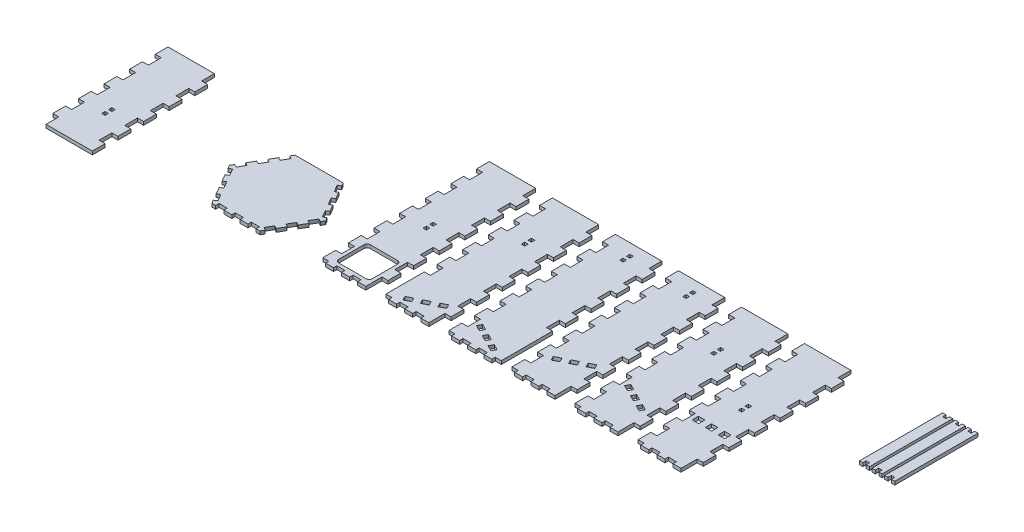
SolidWorks part; units mm, degrees
ref_plane "Front Plane" through (0, 0, 0) normal (0, 0, 1) x (1, 0, 0)
ref_plane "Top Plane" through (0, 0, 0) normal (0, 1, 0) x (1, 0, 0)
ref_plane "Right Plane" through (0, 0, 0) normal (1, 0, 0) x (0, 0, -1)
sketch "Sketch1" plane through (0, 0, 0) normal (0, 1, 0) x (1, 0, 0)
  line L0 (-22.87, -39.612) -> (-19.175, -39.612)
  line L13 (-19.175, -39.612) -> (-19.175, -36.412)
  line L14 (-19.175, -36.412) -> (-11.505, -36.412)
  line L15 (-11.505, -36.412) -> (-11.505, -39.612)
  line L16 (-11.505, -39.612) -> (-3.835, -39.612)
  line L17 (-3.835, -39.612) -> (-3.835, -36.412)
  line L18 (-3.835, -36.412) -> (3.835, -36.412)
  line L19 (3.835, -36.412) -> (3.835, -39.612)
  line L21 (-45.74, 0) -> (-43.8925, -3.2)
  line L22 (3.835, -39.612) -> (11.505, -39.612)
  line L23 (11.505, -39.612) -> (11.505, -36.412)
  line L24 (11.505, -36.412) -> (19.175, -36.412)
  line L25 (19.175, -36.412) -> (19.175, -39.612)
  line L26 (19.175, -39.612) -> (22.87, -39.612)
  line L27 (22.87, -39.612) -> (24.7175, -36.412)
  line L28 (45.74, 0) -> (22.87, 39.612) construction
  line L29 (24.7175, -36.412) -> (21.9462, -34.812)
  line L30 (21.9462, -34.812) -> (25.7812, -28.1696)
  line L31 (25.7812, -28.1696) -> (28.5525, -29.7696)
  line L32 (28.5525, -29.7696) -> (32.3875, -23.1272)
  line L33 (32.3875, -23.1272) -> (29.6162, -21.5272)
  line L34 (29.6162, -21.5272) -> (33.4512, -14.8848)
  line L35 (33.4512, -14.8848) -> (36.2225, -16.4848)
  line L36 (36.2225, -16.4848) -> (40.0575, -9.8424)
  line L37 (40.0575, -9.8424) -> (37.2862, -8.2424)
  line L38 (37.2862, -8.2424) -> (41.1212, -1.6)
  line L39 (41.1212, -1.6) -> (43.8925, -3.2)
  line L40 (43.8925, -3.2) -> (45.74, 0)
  line L41 (45.74, 0) -> (43.8925, 3.2)
  line L42 (22.87, 39.612) -> (-22.87, 39.612) construction
  line L43 (-22.87, 39.612) -> (-45.74, 0) construction
  line L44 (43.8925, 3.2) -> (41.1212, 1.6)
  line L45 (41.1212, 1.6) -> (37.2862, 8.2424)
  line L46 (37.2862, 8.2424) -> (40.0575, 9.8424)
  line L47 (40.0575, 9.8424) -> (36.2225, 16.4848)
  line L48 (36.2225, 16.4848) -> (33.4512, 14.8848)
  line L49 (33.4512, 14.8848) -> (29.6162, 21.5272)
  line L50 (29.6162, 21.5272) -> (32.3875, 23.1272)
  line L51 (32.3875, 23.1272) -> (28.5525, 29.7696)
  line L52 (28.5525, 29.7696) -> (25.7812, 28.1696)
  line L53 (25.7812, 28.1696) -> (21.9462, 34.812)
  line L54 (21.9462, 34.812) -> (24.7175, 36.412)
  line L55 (24.7175, 36.412) -> (22.87, 39.612)
  line L57 (-45.74, 0) -> (-22.87, -39.612) construction
  line L58 (-22.87, -39.612) -> (22.87, -39.612) construction
  line L71 (-22.87, 39.612) -> (-24.7175, 36.412)
  line L72 (22.87, -39.612) -> (45.74, 0) construction
  line L73 (-43.8925, -3.2) -> (-41.1212, -1.6)
  line L74 (-24.7175, 36.412) -> (-21.9462, 34.812)
  line L75 (-21.9462, 34.812) -> (-25.7812, 28.1696)
  line L76 (-25.7812, 28.1696) -> (-28.5525, 29.7696)
  line L77 (-28.5525, 29.7696) -> (-32.3875, 23.1272)
  line L78 (-32.3875, 23.1272) -> (-29.6162, 21.5272)
  line L79 (-29.6162, 21.5272) -> (-33.4512, 14.8848)
  line L80 (-33.4512, 14.8848) -> (-36.2225, 16.4848)
  line L81 (-36.2225, 16.4848) -> (-40.0575, 9.8424)
  line L82 (-40.0575, 9.8424) -> (-37.2862, 8.2424)
  line L83 (-37.2862, 8.2424) -> (-41.1212, 1.6)
  line L84 (-41.1212, 1.6) -> (-43.8925, 3.2)
  line L85 (-43.8925, 3.2) -> (-45.74, 0)
  line L86 (-41.1212, -1.6) -> (-37.2862, -8.2424)
  line L87 (-37.2862, -8.2424) -> (-40.0575, -9.8424)
  line L88 (-40.0575, -9.8424) -> (-36.2225, -16.4848)
  line L89 (-36.2225, -16.4848) -> (-33.4512, -14.8848)
  line L90 (-33.4512, -14.8848) -> (-29.6162, -21.5272)
  line L91 (-29.6162, -21.5272) -> (-32.3875, -23.1272)
  line L92 (-32.3875, -23.1272) -> (-28.5525, -29.7696)
  line L93 (-28.5525, -29.7696) -> (-25.7812, -28.1696)
  line L94 (-25.7812, -28.1696) -> (-21.9462, -34.812)
  line L95 (-21.9462, -34.812) -> (-24.7175, -36.412)
  line L96 (-24.7175, -36.412) -> (-22.87, -39.612)
  line L97 (-21.9462, -34.812) -> (-19.175, -39.612) construction
  line L102 (19.175, -36.412) -> (24.7175, -36.412) construction
  line L103 (-19.175, -36.412) -> (-24.7175, -36.412) construction
  line L104 (80.5528, -34.8794) -> (88.2227, -34.8794)
  line L105 (88.2227, -34.8794) -> (88.2227, -31.6794)
  line L106 (88.2227, -31.6794) -> (95.8927, -31.6794)
  line L107 (95.8927, -31.6794) -> (95.8927, -34.8794)
  line L108 (95.8927, -34.8794) -> (103.5627, -34.8794)
  line L109 (103.5627, -34.8794) -> (103.5627, -31.6794)
  line L110 (103.5627, -31.6794) -> (111.2327, -31.6794)
  line L111 (111.2327, -31.6794) -> (111.2327, -34.8794)
  line L112 (111.2327, -34.8794) -> (118.9027, -34.8794)
  line L113 (80.5528, -34.8794) -> (80.5528, -31.6794)
  line L114 (80.5528, -31.6794) -> (74.8102, -31.6794)
  line L115 (74.8102, -31.6794) -> (74.8102, -19.4911)
  line L116 (74.8102, -19.4911) -> (80.5528, -19.4911)
  line L117 (80.5528, -19.4911) -> (80.5528, -7.3028)
  line L118 (80.5528, -7.3028) -> (74.8102, -7.3028)
  line L121 (118.9027, -7.3028) -> (124.6452, -7.3028)
  line L122 (124.6452, -7.3028) -> (124.6452, -19.4911)
  line L123 (124.6452, -19.4911) -> (118.9027, -19.4911)
  line L124 (118.9027, -19.4911) -> (118.9027, -34.8794)
  line L126 (21.9462, -34.812) -> (19.175, -39.612) construction
  line L250 (140.5528, -34.8794) -> (148.2227, -34.8794)
  line L265 (148.2227, -34.8794) -> (148.2227, -31.6794)
  line L266 (148.2227, -31.6794) -> (155.8927, -31.6794)
  line L267 (155.8927, -31.6794) -> (155.8927, -34.8794)
  line L268 (155.8927, -34.8794) -> (163.5627, -34.8794)
  line L269 (163.5627, -34.8794) -> (163.5627, -31.6794)
  line L270 (74.8102, -7.3028) -> (74.8102, 4.8855)
  line L271 (74.8102, 4.8855) -> (80.5528, 4.8855)
  line L272 (80.5528, 4.8855) -> (80.5528, 17.0739)
  line L273 (80.5528, 17.0739) -> (74.8102, 17.0739)
  line L274 (74.8102, 17.0739) -> (74.8102, 29.2622)
  line L275 (74.8102, 29.2622) -> (80.5528, 29.2622)
  line L276 (80.5528, 29.2622) -> (80.5528, 41.4505)
  line L277 (80.5528, 41.4505) -> (74.8102, 41.4505)
  line L278 (74.8102, 41.4505) -> (74.8102, 53.6388)
  line L279 (74.8102, 53.6388) -> (80.5528, 53.6388)
  line L280 (80.5528, 53.6388) -> (80.5528, 65.8271)
  line L281 (80.5528, 65.8271) -> (74.8102, 65.8271)
  line L282 (74.8102, 65.8271) -> (74.8102, 78.0154)
  line L283 (74.8102, 78.0154) -> (80.5528, 78.0154)
  line L284 (80.5528, 78.0154) -> (80.5528, 90.2037)
  line L285 (80.5528, 90.2037) -> (74.8102, 90.2037)
  line L286 (74.8102, 90.2037) -> (74.8102, 102.392)
  line L287 (74.8102, 102.392) -> (80.5528, 102.392)
  line L288 (80.5528, 102.392) -> (80.5528, 114.5803)
  line L289 (80.5528, 114.5803) -> (74.8102, 114.5803)
  line L290 (74.8102, 114.5803) -> (74.8102, 126.7686)
  line L291 (118.9027, -7.3028) -> (118.9027, 4.8855)
  line L292 (118.9027, 4.8855) -> (124.6452, 4.8855)
  line L293 (124.6452, 4.8855) -> (124.6452, 17.0739)
  line L294 (124.6452, 17.0739) -> (118.9027, 17.0739)
  line L295 (118.9027, 17.0739) -> (118.9027, 29.2622)
  line L296 (118.9027, 29.2622) -> (124.6452, 29.2622)
  line L297 (124.6452, 29.2622) -> (124.6452, 41.4505)
  line L298 (124.6452, 41.4505) -> (118.9027, 41.4505)
  line L299 (118.9027, 41.4505) -> (118.9027, 53.6388)
  line L300 (118.9027, 53.6388) -> (124.6452, 53.6388)
  line L301 (124.6452, 53.6388) -> (124.6452, 65.8271)
  line L302 (124.6452, 65.8271) -> (118.9027, 65.8271)
  line L303 (118.9027, 65.8271) -> (118.9027, 78.0154)
  line L304 (118.9027, 78.0154) -> (124.6452, 78.0154)
  line L305 (124.6452, 78.0154) -> (124.6452, 90.2037)
  line L306 (124.6452, 90.2037) -> (118.9027, 90.2037)
  line L307 (118.9027, 90.2037) -> (118.9027, 102.392)
  line L308 (118.9027, 102.392) -> (124.6452, 102.392)
  line L309 (124.6452, 102.392) -> (124.6452, 114.5803)
  line L310 (124.6452, 114.5803) -> (118.9027, 114.5803)
  line L311 (118.9027, 114.5803) -> (118.9027, 126.7686)
  line L312 (163.5627, -31.6794) -> (171.2327, -31.6794)
  line L313 (171.2327, -31.6794) -> (171.2327, -34.8794)
  line L314 (171.2327, -34.8794) -> (178.9027, -34.8794)
  line L315 (140.5528, -34.8794) -> (140.5528, -31.6794)
  line L316 (140.5528, -31.6794) -> (134.8102, -31.6794)
  line L317 (134.8102, -31.6794) -> (134.8102, -19.4911)
  line L322 (178.9027, -7.3028) -> (184.6452, -7.3028)
  line L323 (184.6452, -7.3028) -> (184.6452, -19.4911)
  line L324 (184.6452, -19.4911) -> (178.9027, -19.4911)
  line L325 (178.9027, -19.4911) -> (178.9027, -34.8794)
  line L326 (134.8102, -7.3028) -> (134.8102, 4.8855)
  line L327 (134.8102, 4.8855) -> (140.5528, 4.8855)
  line L328 (140.5528, 4.8855) -> (140.5528, 17.0739)
  line L329 (140.5528, 17.0739) -> (134.8102, 17.0739)
  line L330 (134.8102, 17.0739) -> (134.8102, 29.2622)
  line L331 (134.8102, 29.2622) -> (140.5528, 29.2622)
  line L332 (140.5528, 29.2622) -> (140.5528, 41.4505)
  line L333 (140.5528, 41.4505) -> (134.8102, 41.4505)
  line L334 (134.8102, 41.4505) -> (134.8102, 53.6388)
  line L335 (134.8102, 53.6388) -> (140.5528, 53.6388)
  line L336 (140.5528, 53.6388) -> (140.5528, 65.8271)
  line L337 (140.5528, 65.8271) -> (134.8102, 65.8271)
  line L338 (134.8102, 65.8271) -> (134.8102, 78.0154)
  line L339 (134.8102, 78.0154) -> (140.5528, 78.0154)
  line L340 (140.5528, 78.0154) -> (140.5528, 90.2037)
  line L341 (140.5528, 90.2037) -> (134.8102, 90.2037)
  line L342 (134.8102, 90.2037) -> (134.8102, 102.392)
  line L343 (134.8102, 102.392) -> (140.5528, 102.392)
  line L344 (140.5528, 102.392) -> (140.5528, 114.5803)
  line L345 (140.5528, 114.5803) -> (134.8102, 114.5803)
  line L346 (134.8102, 114.5803) -> (134.8102, 126.7686)
  line L347 (178.9027, -7.3028) -> (178.9027, 4.8855)
  line L348 (178.9027, 4.8855) -> (184.6452, 4.8855)
  line L349 (184.6452, 4.8855) -> (184.6452, 17.0739)
  line L350 (184.6452, 17.0739) -> (178.9027, 17.0739)
  line L351 (178.9027, 17.0739) -> (178.9027, 29.2622)
  line L352 (178.9027, 29.2622) -> (184.6452, 29.2622)
  line L353 (184.6452, 29.2622) -> (184.6452, 41.4505)
  line L354 (184.6452, 41.4505) -> (178.9027, 41.4505)
  line L355 (178.9027, 41.4505) -> (178.9027, 53.6388)
  line L356 (178.9027, 53.6388) -> (184.6452, 53.6388)
  line L357 (184.6452, 53.6388) -> (184.6452, 65.8271)
  line L358 (184.6452, 65.8271) -> (178.9027, 65.8271)
  line L359 (178.9027, 65.8271) -> (178.9027, 78.0154)
  line L360 (178.9027, 78.0154) -> (184.6452, 78.0154)
  line L361 (184.6452, 78.0154) -> (184.6452, 90.2037)
  line L362 (184.6452, 90.2037) -> (178.9027, 90.2037)
  line L363 (178.9027, 90.2037) -> (178.9027, 102.392)
  line L364 (178.9027, 102.392) -> (184.6452, 102.392)
  line L365 (184.6452, 102.392) -> (184.6452, 114.5803)
  line L366 (184.6452, 114.5803) -> (178.9027, 114.5803)
  line L367 (178.9027, 114.5803) -> (178.9027, 126.7686)
  line L369 (200.5528, -34.8794) -> (208.2227, -34.8794)
  line L370 (208.2227, -34.8794) -> (208.2227, -31.6794)
  line L371 (208.2227, -31.6794) -> (215.8927, -31.6794)
  line L372 (215.8927, -31.6794) -> (215.8927, -34.8794)
  line L373 (215.8927, -34.8794) -> (223.5627, -34.8794)
  line L374 (223.5627, -34.8794) -> (223.5627, -31.6794)
  line L375 (223.5627, -31.6794) -> (231.2327, -31.6794)
  line L376 (231.2327, -31.6794) -> (231.2327, -34.8794)
  line L377 (231.2327, -34.8794) -> (238.9027, -34.8794)
  line L378 (200.5528, -34.8794) -> (200.5528, -31.6794)
  line L379 (200.5528, -31.6794) -> (194.8102, -31.6794)
  line L380 (194.8102, -31.6794) -> (194.8102, -19.4911)
  line L381 (194.8102, -19.4911) -> (200.5528, -19.4911)
  line L382 (200.5528, -19.4911) -> (200.5528, -7.3028)
  line L383 (200.5528, -7.3028) -> (194.8102, -7.3028)
  line L386 (244.6452, -7.3028) -> (244.6452, -19.4911)
  line L389 (194.8102, -7.3028) -> (194.8102, 4.8855)
  line L390 (194.8102, 4.8855) -> (200.5528, 4.8855)
  line L391 (200.5528, 4.8855) -> (200.5528, 17.0739)
  line L392 (200.5528, 17.0739) -> (194.8102, 17.0739)
  line L393 (194.8102, 17.0739) -> (194.8102, 29.2622)
  line L394 (194.8102, 29.2622) -> (200.5528, 29.2622)
  line L395 (200.5528, 29.2622) -> (200.5528, 41.4505)
  line L396 (200.5528, 41.4505) -> (194.8102, 41.4505)
  line L397 (194.8102, 41.4505) -> (194.8102, 53.6388)
  line L398 (194.8102, 53.6388) -> (200.5528, 53.6388)
  line L399 (200.5528, 53.6388) -> (200.5528, 65.8271)
  line L400 (200.5528, 65.8271) -> (194.8102, 65.8271)
  line L401 (194.8102, 65.8271) -> (194.8102, 78.0154)
  line L402 (194.8102, 78.0154) -> (200.5528, 78.0154)
  line L403 (200.5528, 78.0154) -> (200.5528, 90.2037)
  line L404 (200.5528, 90.2037) -> (194.8102, 90.2037)
  line L405 (194.8102, 90.2037) -> (194.8102, 102.392)
  line L406 (194.8102, 102.392) -> (200.5528, 102.392)
  line L407 (200.5528, 102.392) -> (200.5528, 114.5803)
  line L408 (200.5528, 114.5803) -> (194.8102, 114.5803)
  line L409 (194.8102, 114.5803) -> (194.8102, 126.7686)
  line L413 (244.6452, 17.0739) -> (238.9027, 17.0739)
  line L414 (238.9027, 17.0739) -> (238.9027, 29.2622)
  line L415 (238.9027, 29.2622) -> (244.6452, 29.2622)
  line L416 (244.6452, 29.2622) -> (244.6452, 41.4505)
  line L417 (244.6452, 41.4505) -> (238.9027, 41.4505)
  line L418 (238.9027, 41.4505) -> (238.9027, 53.6388)
  line L419 (238.9027, 53.6388) -> (244.6452, 53.6388)
  line L420 (244.6452, 53.6388) -> (244.6452, 65.8271)
  line L421 (244.6452, 65.8271) -> (238.9027, 65.8271)
  line L422 (238.9027, 65.8271) -> (238.9027, 78.0154)
  line L423 (238.9027, 78.0154) -> (244.6452, 78.0154)
  line L424 (244.6452, 78.0154) -> (244.6452, 90.2037)
  line L425 (244.6452, 90.2037) -> (238.9027, 90.2037)
  line L426 (238.9027, 90.2037) -> (238.9027, 102.392)
  line L427 (238.9027, 102.392) -> (244.6452, 102.392)
  line L428 (244.6452, 102.392) -> (244.6452, 114.5803)
  line L429 (244.6452, 114.5803) -> (238.9027, 114.5803)
  line L430 (238.9027, 114.5803) -> (238.9027, 126.7686)
  line L432 (260.5528, -34.8794) -> (268.2227, -34.8794)
  line L433 (268.2227, -34.8794) -> (268.2227, -31.6794)
  line L434 (268.2227, -31.6794) -> (275.8927, -31.6794)
  line L435 (275.8927, -31.6794) -> (275.8927, -34.8794)
  line L436 (275.8927, -34.8794) -> (283.5627, -34.8794)
  line L437 (283.5627, -34.8794) -> (283.5627, -31.6794)
  line L438 (283.5627, -31.6794) -> (291.2327, -31.6794)
  line L439 (291.2327, -31.6794) -> (291.2327, -34.8794)
  line L440 (291.2327, -34.8794) -> (298.9027, -34.8794)
  line L441 (260.5528, -34.8794) -> (260.5528, -31.6794)
  line L442 (260.5528, -31.6794) -> (254.8102, -31.6794)
  line L443 (254.8102, -31.6794) -> (254.8102, -19.4911)
  line L444 (254.8102, -19.4911) -> (260.5528, -19.4911)
  line L445 (260.5528, -19.4911) -> (260.5528, -7.3028)
  line L446 (260.5528, -7.3028) -> (254.8102, -7.3028)
  line L448 (298.9027, -7.3028) -> (304.6452, -7.3028)
  line L449 (304.6452, -7.3028) -> (304.6452, -19.4911)
  line L450 (304.6452, -19.4911) -> (298.9027, -19.4911)
  line L451 (298.9027, -19.4911) -> (298.9027, -34.8794)
  line L452 (254.8102, -7.3028) -> (254.8102, 4.8855)
  line L453 (254.8102, 4.8855) -> (260.5528, 4.8855)
  line L454 (260.5528, 4.8855) -> (260.5528, 17.0739)
  line L455 (260.5528, 17.0739) -> (254.8102, 17.0739)
  line L456 (254.8102, 17.0739) -> (254.8102, 29.2622)
  line L457 (254.8102, 29.2622) -> (260.5528, 29.2622)
  line L458 (260.5528, 29.2622) -> (260.5528, 41.4505)
  line L459 (260.5528, 41.4505) -> (254.8102, 41.4505)
  line L460 (254.8102, 41.4505) -> (254.8102, 53.6388)
  line L461 (254.8102, 53.6388) -> (260.5528, 53.6388)
  line L462 (260.5528, 53.6388) -> (260.5528, 65.8271)
  line L463 (260.5528, 65.8271) -> (254.8102, 65.8271)
  line L464 (254.8102, 65.8271) -> (254.8102, 78.0154)
  line L465 (254.8102, 78.0154) -> (260.5528, 78.0154)
  line L466 (260.5528, 78.0154) -> (260.5528, 90.2037)
  line L467 (260.5528, 90.2037) -> (254.8102, 90.2037)
  line L468 (254.8102, 90.2037) -> (254.8102, 102.392)
  line L469 (254.8102, 102.392) -> (260.5528, 102.392)
  line L470 (260.5528, 102.392) -> (260.5528, 114.5803)
  line L471 (260.5528, 114.5803) -> (254.8102, 114.5803)
  line L472 (254.8102, 114.5803) -> (254.8102, 126.7686)
  line L473 (298.9027, -7.3028) -> (298.9027, 4.8855)
  line L474 (298.9027, 4.8855) -> (304.6452, 4.8855)
  line L475 (304.6452, 4.8855) -> (304.6452, 17.0739)
  line L476 (304.6452, 17.0739) -> (298.9027, 17.0739)
  line L477 (298.9027, 17.0739) -> (298.9027, 29.2622)
  line L478 (298.9027, 29.2622) -> (304.6452, 29.2622)
  line L479 (304.6452, 29.2622) -> (304.6452, 41.4505)
  line L480 (304.6452, 41.4505) -> (298.9027, 41.4505)
  line L481 (298.9027, 41.4505) -> (298.9027, 53.6388)
  line L482 (298.9027, 53.6388) -> (304.6452, 53.6388)
  line L483 (304.6452, 53.6388) -> (304.6452, 65.8271)
  line L484 (304.6452, 65.8271) -> (298.9027, 65.8271)
  line L485 (298.9027, 65.8271) -> (298.9027, 78.0154)
  line L486 (298.9027, 78.0154) -> (304.6452, 78.0154)
  line L487 (304.6452, 78.0154) -> (304.6452, 90.2037)
  line L488 (304.6452, 90.2037) -> (298.9027, 90.2037)
  line L489 (298.9027, 90.2037) -> (298.9027, 102.392)
  line L490 (298.9027, 102.392) -> (304.6452, 102.392)
  line L491 (304.6452, 102.392) -> (304.6452, 114.5803)
  line L492 (304.6452, 114.5803) -> (298.9027, 114.5803)
  line L493 (298.9027, 114.5803) -> (298.9027, 126.7686)
  line L495 (320.5528, -34.8794) -> (328.2227, -34.8794)
  line L496 (328.2227, -34.8794) -> (328.2227, -31.6794)
  line L497 (328.2227, -31.6794) -> (335.8927, -31.6794)
  line L498 (335.8927, -31.6794) -> (335.8927, -34.8794)
  line L499 (335.8927, -34.8794) -> (343.5627, -34.8794)
  line L500 (343.5627, -34.8794) -> (343.5627, -31.6794)
  line L501 (343.5627, -31.6794) -> (351.2327, -31.6794)
  line L502 (351.2327, -31.6794) -> (351.2327, -34.8794)
  line L503 (351.2327, -34.8794) -> (358.9027, -34.8794)
  line L504 (320.5528, -34.8794) -> (320.5528, -31.6794)
  line L505 (320.5528, -31.6794) -> (314.8102, -31.6794)
  line L506 (314.8102, -31.6794) -> (314.8102, -19.4911)
  line L507 (314.8102, -19.4911) -> (320.5528, -19.4911)
  line L508 (320.5528, -19.4911) -> (320.5528, -7.3028)
  line L509 (320.5528, -7.3028) -> (314.8102, -7.3028)
  line L511 (358.9027, -7.3028) -> (364.6452, -7.3028)
  line L512 (364.6452, -7.3028) -> (364.6452, -19.4911)
  line L513 (364.6452, -19.4911) -> (358.9027, -19.4911)
  line L514 (358.9027, -19.4911) -> (358.9027, -34.8794)
  line L515 (314.8102, -7.3028) -> (314.8102, 4.8855)
  line L516 (314.8102, 4.8855) -> (320.5528, 4.8855)
  line L517 (320.5528, 4.8855) -> (320.5528, 17.0739)
  line L518 (320.5528, 17.0739) -> (314.8102, 17.0739)
  line L519 (314.8102, 17.0739) -> (314.8102, 29.2622)
  line L520 (314.8102, 29.2622) -> (320.5528, 29.2622)
  line L521 (320.5528, 29.2622) -> (320.5528, 41.4505)
  line L522 (320.5528, 41.4505) -> (314.8102, 41.4505)
  line L523 (314.8102, 41.4505) -> (314.8102, 53.6388)
  line L524 (314.8102, 53.6388) -> (320.5528, 53.6388)
  line L525 (320.5528, 53.6388) -> (320.5528, 65.8271)
  line L526 (320.5528, 65.8271) -> (314.8102, 65.8271)
  line L527 (314.8102, 65.8271) -> (314.8102, 78.0154)
  line L528 (314.8102, 78.0154) -> (320.5528, 78.0154)
  line L529 (320.5528, 78.0154) -> (320.5528, 90.2037)
  line L530 (320.5528, 90.2037) -> (314.8102, 90.2037)
  line L531 (314.8102, 90.2037) -> (314.8102, 102.392)
  line L532 (314.8102, 102.392) -> (320.5528, 102.392)
  line L533 (320.5528, 102.392) -> (320.5528, 114.5803)
  line L534 (320.5528, 114.5803) -> (314.8102, 114.5803)
  line L535 (314.8102, 114.5803) -> (314.8102, 126.7686)
  line L536 (358.9027, -7.3028) -> (358.9027, 4.8855)
  line L537 (358.9027, 4.8855) -> (364.6452, 4.8855)
  line L538 (364.6452, 4.8855) -> (364.6452, 17.0739)
  line L539 (364.6452, 17.0739) -> (358.9027, 17.0739)
  line L540 (358.9027, 17.0739) -> (358.9027, 29.2622)
  line L541 (358.9027, 29.2622) -> (364.6452, 29.2622)
  line L542 (364.6452, 29.2622) -> (364.6452, 41.4505)
  line L543 (364.6452, 41.4505) -> (358.9027, 41.4505)
  line L544 (358.9027, 41.4505) -> (358.9027, 53.6388)
  line L545 (358.9027, 53.6388) -> (364.6452, 53.6388)
  line L546 (364.6452, 53.6388) -> (364.6452, 65.8271)
  line L547 (364.6452, 65.8271) -> (358.9027, 65.8271)
  line L548 (358.9027, 65.8271) -> (358.9027, 78.0154)
  line L549 (358.9027, 78.0154) -> (364.6452, 78.0154)
  line L550 (364.6452, 78.0154) -> (364.6452, 90.2037)
  line L551 (364.6452, 90.2037) -> (358.9027, 90.2037)
  line L552 (358.9027, 90.2037) -> (358.9027, 102.392)
  line L553 (358.9027, 102.392) -> (364.6452, 102.392)
  line L554 (364.6452, 102.392) -> (364.6452, 114.5803)
  line L555 (364.6452, 114.5803) -> (358.9027, 114.5803)
  line L556 (358.9027, 114.5803) -> (358.9027, 126.7686)
  line L558 (380.5528, -34.8794) -> (388.2227, -34.8794)
  line L559 (388.2227, -34.8794) -> (388.2227, -31.6794)
  line L560 (388.2227, -31.6794) -> (395.8927, -31.6794)
  line L561 (395.8927, -31.6794) -> (395.8927, -34.8794)
  line L562 (395.8927, -34.8794) -> (403.5627, -34.8794)
  line L563 (403.5627, -34.8794) -> (403.5627, -31.6794)
  line L564 (403.5627, -31.6794) -> (411.2327, -31.6794)
  line L565 (411.2327, -31.6794) -> (411.2327, -34.8794)
  line L566 (411.2327, -34.8794) -> (418.9027, -34.8794)
  line L567 (380.5528, -34.8794) -> (380.5528, -31.6794)
  line L568 (380.5528, -31.6794) -> (374.8102, -31.6794)
  line L569 (374.8102, -31.6794) -> (374.8102, -19.4911)
  line L570 (374.8102, -19.4911) -> (380.5528, -19.4911)
  line L571 (380.5528, -19.4911) -> (380.5528, -7.3028)
  line L572 (380.5528, -7.3028) -> (374.8102, -7.3028)
  line L574 (418.9027, -7.3028) -> (424.6452, -7.3028)
  line L575 (424.6452, -7.3028) -> (424.6452, -19.4911)
  line L576 (424.6452, -19.4911) -> (418.9027, -19.4911)
  line L577 (418.9027, -19.4911) -> (418.9027, -34.8794)
  line L578 (374.8102, -7.3028) -> (374.8102, 4.8855)
  line L579 (374.8102, 4.8855) -> (380.5528, 4.8855)
  line L580 (380.5528, 4.8855) -> (380.5528, 17.0739)
  line L581 (380.5528, 17.0739) -> (374.8102, 17.0739)
  line L582 (374.8102, 17.0739) -> (374.8102, 29.2622)
  line L583 (374.8102, 29.2622) -> (380.5528, 29.2622)
  line L584 (380.5528, 29.2622) -> (380.5528, 41.4505)
  line L585 (380.5528, 41.4505) -> (374.8102, 41.4505)
  line L586 (374.8102, 41.4505) -> (374.8102, 53.6388)
  line L587 (374.8102, 53.6388) -> (380.5528, 53.6388)
  line L588 (380.5528, 53.6388) -> (380.5528, 65.8271)
  line L589 (380.5528, 65.8271) -> (374.8102, 65.8271)
  line L590 (374.8102, 65.8271) -> (374.8102, 78.0154)
  line L591 (374.8102, 78.0154) -> (380.5528, 78.0154)
  line L592 (380.5528, 78.0154) -> (380.5528, 90.2037)
  line L593 (380.5528, 90.2037) -> (374.8102, 90.2037)
  line L594 (374.8102, 90.2037) -> (374.8102, 102.392)
  line L595 (374.8102, 102.392) -> (380.5528, 102.392)
  line L596 (380.5528, 102.392) -> (380.5528, 114.5803)
  line L597 (380.5528, 114.5803) -> (374.8102, 114.5803)
  line L598 (374.8102, 114.5803) -> (374.8102, 126.7686)
  line L599 (418.9027, -7.3028) -> (418.9027, 4.8855)
  line L600 (418.9027, 4.8855) -> (424.6452, 4.8855)
  line L601 (424.6452, 4.8855) -> (424.6452, 17.0739)
  line L602 (424.6452, 17.0739) -> (418.9027, 17.0739)
  line L603 (418.9027, 17.0739) -> (418.9027, 29.2622)
  line L604 (418.9027, 29.2622) -> (424.6452, 29.2622)
  line L605 (424.6452, 29.2622) -> (424.6452, 41.4505)
  line L606 (424.6452, 41.4505) -> (418.9027, 41.4505)
  line L607 (418.9027, 41.4505) -> (418.9027, 53.6388)
  line L608 (418.9027, 53.6388) -> (424.6452, 53.6388)
  line L609 (424.6452, 53.6388) -> (424.6452, 65.8271)
  line L610 (424.6452, 65.8271) -> (418.9027, 65.8271)
  line L611 (418.9027, 65.8271) -> (418.9027, 78.0154)
  line L612 (418.9027, 78.0154) -> (424.6452, 78.0154)
  line L613 (424.6452, 78.0154) -> (424.6452, 90.2037)
  line L614 (424.6452, 90.2037) -> (418.9027, 90.2037)
  line L615 (418.9027, 90.2037) -> (418.9027, 102.392)
  line L616 (418.9027, 102.392) -> (424.6452, 102.392)
  line L617 (424.6452, 102.392) -> (424.6452, 114.5803)
  line L618 (424.6452, 114.5803) -> (418.9027, 114.5803)
  line L619 (418.9027, 114.5803) -> (418.9027, 126.7686)
  line L621 (145.8635, -24.5223) -> (151.4092, -21.7501)
  line L622 (145.8635, -24.5223) -> (147.8308, -28.458)
  line L623 (147.8308, -28.458) -> (153.3765, -25.6858)
  line L624 (151.4092, -21.7501) -> (153.3765, -25.6858)
  line L625 (156.9549, -18.9779) -> (162.5006, -16.2057)
  line L626 (156.9549, -18.9779) -> (158.9222, -22.9135)
  line L627 (158.9222, -22.9135) -> (164.4679, -20.1413)
  line L628 (162.5006, -16.2057) -> (164.4679, -20.1413)
  line L632 (168.0463, -13.4335) -> (173.592, -10.6612)
  line L633 (168.0463, -13.4335) -> (170.0136, -17.3691)
  line L634 (170.0136, -17.3691) -> (175.5593, -14.5969)
  line L635 (173.592, -10.6612) -> (175.5593, -14.5969)
  line L636 (118.9027, 126.7686) -> (74.8102, 126.7686)
  line L637 (134.8102, 126.7686) -> (178.9027, 126.7686)
  line L638 (194.8102, 126.7686) -> (238.9027, 126.7686)
  line L639 (254.8102, 126.7686) -> (298.9027, 126.7686)
  line L640 (314.8102, 126.7686) -> (358.9027, 126.7686)
  line L641 (374.8102, 126.7686) -> (418.9027, 126.7686)
  line L642 (-41.1212, -1.6) -> (-42.045, 0) construction
  line L643 (-42.045, 0) -> (-41.1212, 1.6) construction
  line L644 (41.1212, -1.6) -> (42.045, 0) construction
  line L645 (42.045, 0) -> (41.1212, 1.6) construction
  line L646 (-21.0225, -36.412) -> (-22.87, -39.612) construction
  line L647 (21.0225, -36.412) -> (22.87, -39.612) construction
  line L648 (138.7077, -28.0994) -> (145.8635, -24.5223) construction
  line L649 (173.592, -10.6612) -> (180.7477, -7.0842) construction
  line L650 (189.7277, 136.633) -> (189.7277, -43.0289) construction
  line L651 (138.7077, -34.8794) -> (180.7477, -34.8794) construction
  line L652 (205.8635, -10.6612) -> (203.8961, -14.5969)
  line L653 (209.4418, -17.3691) -> (203.8961, -14.5969)
  line L654 (211.4092, -13.4335) -> (209.4418, -17.3691)
  line L655 (211.4092, -13.4335) -> (205.8635, -10.6612)
  line L656 (216.9549, -16.2057) -> (214.9875, -20.1413)
  line L657 (220.5332, -22.9135) -> (214.9875, -20.1413)
  line L658 (222.5006, -18.9779) -> (220.5332, -22.9135)
  line L659 (222.5006, -18.9779) -> (216.9549, -16.2057)
  line L660 (228.0463, -21.7501) -> (226.0789, -25.6858)
  line L661 (231.6246, -28.458) -> (226.0789, -25.6858)
  line L662 (233.592, -24.5223) -> (231.6246, -28.458)
  line L663 (233.592, -24.5223) -> (228.0463, -21.7501)
  line L664 (252.6938, -7.0794) -> (309.7277, -7.0794) construction
  line L665 (258.7077, -34.8794) -> (300.7477, -34.8794) construction
  line L666 (258.7077, -11.9985) -> (267.8308, -7.438) construction
  line L667 (267.8308, -7.438) -> (265.8635, -3.5023)
  line L668 (265.8635, -3.5023) -> (271.4092, -0.7301)
  line L669 (271.4092, -0.7301) -> (273.3765, -4.6658)
  line L670 (273.3765, -4.6658) -> (267.8308, -7.438)
  line L671 (276.9549, 2.0421) -> (278.9222, -1.8935)
  line L672 (278.9222, -1.8935) -> (284.4679, 0.8787)
  line L673 (284.4679, 0.8787) -> (282.5006, 4.8143)
  line L674 (282.5006, 4.8143) -> (276.9549, 2.0421)
  line L675 (288.0463, 7.5865) -> (290.0136, 3.6509)
  line L676 (290.0136, 3.6509) -> (295.5593, 6.4231)
  line L677 (295.5593, 6.4231) -> (293.592, 10.3588)
  line L678 (293.592, 10.3588) -> (288.0463, 7.5865)
  line L679 (295.5593, 6.4231) -> (300.7477, 9.0167) construction
  line L680 (309.7277, 136.633) -> (309.7277, -43.0289) construction
  line L681 (325.8635, 10.3588) -> (331.4092, 7.5865)
  line L682 (323.8961, 6.4231) -> (325.8635, 10.3588)
  line L683 (329.4418, 3.6509) -> (323.8961, 6.4231)
  line L684 (331.4092, 7.5865) -> (329.4418, 3.6509)
  line L685 (336.9549, 4.8143) -> (342.5006, 2.0421)
  line L686 (334.9875, 0.8787) -> (336.9549, 4.8143)
  line L687 (340.5332, -1.8935) -> (334.9875, 0.8787)
  line L688 (342.5006, 2.0421) -> (340.5332, -1.8935)
  line L689 (346.0789, -4.6658) -> (351.6246, -7.438)
  line L690 (348.0463, -0.7301) -> (346.0789, -4.6658)
  line L691 (353.592, -3.5023) -> (348.0463, -0.7301)
  line L692 (351.6246, -7.438) -> (353.592, -3.5023)
  line L693 (384.2277, 16.3606) -> (384.2277, 10.3606)
  line L694 (384.2277, 10.3606) -> (390.4277, 10.3606)
  line L695 (390.4277, 10.3606) -> (390.4277, 16.3606)
  line L696 (390.4277, 16.3606) -> (384.2277, 16.3606)
  line L697 (396.6277, 16.3606) -> (396.6277, 10.3606)
  line L698 (396.6277, 10.3606) -> (402.8277, 10.3606)
  line L699 (402.8277, 10.3606) -> (402.8277, 16.3606)
  line L700 (402.8277, 16.3606) -> (396.6277, 16.3606)
  line L701 (409.0277, 16.3606) -> (409.0277, 10.3606)
  line L702 (409.0277, 10.3606) -> (415.2277, 10.3606)
  line L703 (415.2277, 10.3606) -> (415.2277, 16.3606)
  line L704 (415.2277, 16.3606) -> (409.0277, 16.3606)
  line L705 (384.2277, 10.3606) -> (380.5528, 10.3606) construction
  line L706 (415.2277, 10.3606) -> (418.9027, 10.3606) construction
  line L707 (86.7528, 1.5206) -> (112.7027, 1.5206)
  line L708 (112.7027, -28.4794) -> (86.7528, -28.4794)
  line L709 (83.7528, -1.4794) -> (83.7528, -25.4794)
  line L710 (115.7027, -1.4794) -> (115.7027, -25.4794)
  line L711 (249.7277, 136.633) -> (249.7277, -43.0289) construction
  line L712 (398.1277, 49.9606) -> (401.3277, 49.9606)
  line L713 (398.1277, 49.9606) -> (398.1277, 46.7606)
  line L714 (398.1277, 46.7606) -> (401.3277, 46.7606)
  line L715 (401.3277, 49.9606) -> (401.3277, 46.7606)
  line L716 (398.1277, 43.5606) -> (401.3277, 43.5606)
  line L717 (398.1277, 43.5606) -> (398.1277, 40.3606)
  line L718 (398.1277, 40.3606) -> (401.3277, 40.3606)
  line L719 (401.3277, 43.5606) -> (401.3277, 40.3606)
  line L720 (98.1277, 43.5606) -> (98.1277, 40.3606)
  line L721 (101.3277, 40.3606) -> (98.1277, 40.3606)
  line L722 (101.3277, 43.5606) -> (101.3277, 40.3606)
  line L723 (101.3277, 43.5606) -> (98.1277, 43.5606)
  line L724 (98.1277, 49.9606) -> (98.1277, 46.7606)
  line L725 (101.3277, 46.7606) -> (98.1277, 46.7606)
  line L726 (101.3277, 49.9606) -> (101.3277, 46.7606)
  line L727 (101.3277, 49.9606) -> (98.1277, 49.9606)
  line L728 (158.1277, 77.1606) -> (158.1277, 73.9606)
  line L729 (161.3277, 73.9606) -> (158.1277, 73.9606)
  line L730 (161.3277, 77.1606) -> (161.3277, 73.9606)
  line L731 (161.3277, 77.1606) -> (158.1277, 77.1606)
  line L732 (158.1277, 83.5606) -> (158.1277, 80.3606)
  line L733 (161.3277, 80.3606) -> (158.1277, 80.3606)
  line L734 (161.3277, 83.5606) -> (161.3277, 80.3606)
  line L735 (161.3277, 83.5606) -> (158.1277, 83.5606)
  line L736 (338.1277, 83.5606) -> (341.3277, 83.5606)
  line L737 (338.1277, 83.5606) -> (338.1277, 80.3606)
  line L738 (338.1277, 80.3606) -> (341.3277, 80.3606)
  line L739 (341.3277, 83.5606) -> (341.3277, 80.3606)
  line L740 (338.1277, 77.1606) -> (341.3277, 77.1606)
  line L741 (338.1277, 77.1606) -> (338.1277, 73.9606)
  line L742 (338.1277, 73.9606) -> (341.3277, 73.9606)
  line L743 (341.3277, 77.1606) -> (341.3277, 73.9606)
  line L744 (218.1277, 110.7606) -> (218.1277, 107.5606)
  line L745 (221.3277, 107.5606) -> (218.1277, 107.5606)
  line L746 (221.3277, 110.7606) -> (221.3277, 107.5606)
  line L747 (221.3277, 110.7606) -> (218.1277, 110.7606)
  line L748 (218.1277, 117.1606) -> (218.1277, 113.9606)
  line L749 (221.3277, 113.9606) -> (218.1277, 113.9606)
  line L750 (221.3277, 117.1606) -> (221.3277, 113.9606)
  line L751 (221.3277, 117.1606) -> (218.1277, 117.1606)
  line L752 (278.1277, 117.1606) -> (281.3277, 117.1606)
  line L753 (278.1277, 117.1606) -> (278.1277, 113.9606)
  line L754 (278.1277, 113.9606) -> (281.3277, 113.9606)
  line L755 (281.3277, 117.1606) -> (281.3277, 113.9606)
  line L756 (278.1277, 110.7606) -> (281.3277, 110.7606)
  line L757 (278.1277, 110.7606) -> (278.1277, 107.5606)
  line L758 (278.1277, 107.5606) -> (281.3277, 107.5606)
  line L759 (281.3277, 110.7606) -> (281.3277, 107.5606)
  line L760 (497.6107, 135.4038) -> (497.6107, 56.1838)
  line L761 (500.8107, 56.1838) -> (500.8107, 59.3838)
  line L762 (500.8107, 59.3838) -> (504.0107, 59.3838)
  line L763 (504.0107, 59.3838) -> (504.0107, 56.1838)
  line L764 (504.0107, 56.1838) -> (507.2107, 56.1838)
  line L765 (507.2107, 56.1838) -> (507.2107, 135.4038)
  line L766 (507.2107, 135.4038) -> (504.0107, 135.4038)
  line L767 (504.0107, 135.4038) -> (504.0107, 132.2038)
  line L768 (504.0107, 132.2038) -> (500.8107, 132.2038)
  line L769 (500.8107, 132.2038) -> (500.8107, 135.4038)
  line L770 (500.8107, 135.4038) -> (497.6107, 135.4038)
  line L771 (500.8107, 56.1838) -> (497.6107, 56.1838)
  line L772 (509.6107, 135.4038) -> (509.6107, 56.1838)
  line L773 (512.8107, 56.1838) -> (512.8107, 59.3838)
  line L774 (512.8107, 59.3838) -> (516.0107, 59.3838)
  line L775 (516.0107, 59.3838) -> (516.0107, 56.1838)
  line L776 (516.0107, 56.1838) -> (519.2107, 56.1838)
  line L777 (519.2107, 56.1838) -> (519.2107, 135.4038)
  line L778 (519.2107, 135.4038) -> (516.0107, 135.4038)
  line L779 (516.0107, 135.4038) -> (516.0107, 132.2038)
  line L780 (516.0107, 132.2038) -> (512.8107, 132.2038)
  line L781 (512.8107, 132.2038) -> (512.8107, 135.4038)
  line L782 (512.8107, 135.4038) -> (509.6107, 135.4038)
  line L783 (512.8107, 56.1838) -> (509.6107, 56.1838)
  line L784 (521.6107, 135.4038) -> (521.6107, 56.1838)
  line L785 (524.8107, 56.1838) -> (524.8107, 59.3838)
  line L786 (524.8107, 59.3838) -> (528.0107, 59.3838)
  line L787 (528.0107, 59.3838) -> (528.0107, 56.1838)
  line L788 (528.0107, 56.1838) -> (531.2107, 56.1838)
  line L789 (531.2107, 56.1838) -> (531.2107, 135.4038)
  line L790 (531.2107, 135.4038) -> (528.0107, 135.4038)
  line L791 (528.0107, 135.4038) -> (528.0107, 132.2038)
  line L792 (528.0107, 132.2038) -> (524.8107, 132.2038)
  line L793 (524.8107, 132.2038) -> (524.8107, 135.4038)
  line L794 (524.8107, 135.4038) -> (521.6107, 135.4038)
  line L795 (524.8107, 56.1838) -> (521.6107, 56.1838)
  line L796 (265.8635, -3.5023) -> (258.7077, -7.0794) construction
  line L797 (293.592, 10.3588) -> (300.7477, 13.9358) construction
  line L798 (-22.87, 39.612) -> (22.87, 39.612)
  line L820 (-166.7844, -53.5158) -> (-166.7844, -41.3275)
  line L821 (-166.7844, -41.3275) -> (-172.527, -41.3275)
  line L822 (-172.527, -41.3275) -> (-172.527, -29.1392)
  line L823 (-172.527, -29.1392) -> (-166.7844, -29.1392)
  line L824 (-166.7844, -29.1392) -> (-166.7844, -16.9509)
  line L825 (-166.7844, -16.9509) -> (-172.527, -16.9509)
  line L826 (-172.527, -16.9509) -> (-172.527, -4.7626)
  line L827 (-172.527, -4.7626) -> (-166.7844, -4.7626)
  line L828 (-166.7844, -4.7626) -> (-166.7844, 7.4257)
  line L829 (-166.7844, 7.4257) -> (-172.527, 7.4257)
  line L830 (-172.527, 7.4257) -> (-172.527, 19.614)
  line L831 (-172.527, 19.614) -> (-166.7844, 19.614)
  line L832 (-166.7844, 19.614) -> (-166.7844, 31.8023)
  line L833 (-166.7844, 31.8023) -> (-172.527, 31.8023)
  line L834 (-172.527, 31.8023) -> (-172.527, 43.9906)
  line L835 (-172.527, 43.9906) -> (-166.7844, 43.9906)
  line L836 (-166.7844, 43.9906) -> (-166.7844, 56.1789)
  line L837 (-166.7844, 56.1789) -> (-172.527, 56.1789)
  line L838 (-172.527, 56.1789) -> (-172.527, 68.3672)
  line L841 (-122.6919, -53.5158) -> (-122.6919, -41.3275)
  line L842 (-122.6919, -41.3275) -> (-128.4345, -41.3275)
  line L843 (-128.4345, -41.3275) -> (-128.4345, -29.1392)
  line L844 (-128.4345, -29.1392) -> (-122.6919, -29.1392)
  line L845 (-122.6919, -29.1392) -> (-122.6919, -16.9509)
  line L846 (-122.6919, -16.9509) -> (-128.4345, -16.9509)
  line L847 (-128.4345, -16.9509) -> (-128.4345, -4.7626)
  line L848 (-128.4345, -4.7626) -> (-122.6919, -4.7626)
  line L849 (-122.6919, -4.7626) -> (-122.6919, 7.4257)
  line L850 (-122.6919, 7.4257) -> (-128.4345, 7.4257)
  line L851 (-128.4345, 7.4257) -> (-128.4345, 19.614)
  line L852 (-128.4345, 19.614) -> (-122.6919, 19.614)
  line L853 (-122.6919, 19.614) -> (-122.6919, 31.8023)
  line L854 (-122.6919, 31.8023) -> (-128.4345, 31.8023)
  line L855 (-128.4345, 31.8023) -> (-128.4345, 43.9906)
  line L856 (-128.4345, 43.9906) -> (-122.6919, 43.9906)
  line L857 (-122.6919, 43.9906) -> (-122.6919, 56.1789)
  line L858 (-122.6919, 56.1789) -> (-128.4345, 56.1789)
  line L859 (-128.4345, 56.1789) -> (-128.4345, 68.3672)
  line L860 (-128.4345, 68.3672) -> (-172.527, 68.3672)
  line L865 (-149.2095, -14.8408) -> (-149.2095, -18.0408)
  line L866 (-146.0095, -18.0408) -> (-149.2095, -18.0408)
  line L867 (-146.0095, -14.8408) -> (-146.0095, -18.0408)
  line L868 (-146.0095, -14.8408) -> (-149.2095, -14.8408)
  line L869 (-149.2095, -8.4408) -> (-149.2095, -11.6408)
  line L870 (-146.0095, -11.6408) -> (-149.2095, -11.6408)
  line L871 (-146.0095, -8.4408) -> (-146.0095, -11.6408)
  line L872 (-146.0095, -8.4408) -> (-149.2095, -8.4408)
  line L873 (-166.7844, -53.5158) -> (-122.6919, -53.5158)
  line L874 (134.8102, -19.4911) -> (134.8102, -7.3028)
  line L876 (140.5528, -19.4911) -> (140.5528, -7.3028) [skipped]
  line L877 (134.8102, -19.4911) -> (140.5528, -19.4911) [skipped]
  line L878 (140.5528, -7.3028) -> (134.8102, -7.3028) [skipped]
  line L879 (244.6452, -31.6794) -> (238.9027, -31.6794)
  line L880 (238.9027, -31.6794) -> (238.9027, -34.8794)
  line L881 (244.6452, -19.4911) -> (244.6452, -31.6794)
  line L882 (238.9027, -19.4911) -> (238.9027, -34.8794) [skipped]
  line L883 (244.6452, -19.4911) -> (238.9027, -19.4911) [skipped]
  line L884 (244.6452, 17.0739) -> (244.6452, -7.3028)
  line L885 (238.9027, -7.3028) -> (244.6452, -7.3028) [skipped]
  line L886 (238.9027, -7.3028) -> (238.9027, 4.8855) [skipped]
  line L887 (238.9027, 4.8855) -> (244.6452, 4.8855) [skipped]
  line L888 (244.6452, 4.8855) -> (244.6452, 17.0739) [skipped]
  circle A0 centre (0, 0) radius 39.612 construction
  arc A5 (86.7528, -28.4794) -> (83.7528, -25.4794) centre (86.7528, -25.4794) cw
  arc A6 (83.7528, -1.4794) -> (86.7528, 1.5206) centre (86.7528, -1.4794) cw
  arc A7 (112.7027, 1.5206) -> (115.7027, -1.4794) centre (112.7027, -1.4794) cw
  arc A8 (115.7027, -25.4794) -> (112.7027, -28.4794) centre (112.7027, -25.4794) cw
  point P498 (304.6452, -13.3969)
  point P582 (158.1277, 81.9606)
  dimension "D9" = 79.224
  dimension "D66" = 38.3499
  dimension "D79" = 3.2
  dimension "D10" = 38.3499
  dimension "D83" = 5.7426
  dimension "D45" = 5.7426
  dimension "D2" = 3.695
  dimension "D3" = 7.67
  dimension "D5" = 38.3499
  dimension "D11" = 12.1883
  dimension "D13" = 3.2
  dimension "D14" = 5.5426
  dimension "D86" = 15.3883
  dimension "D17" = 6.2
  dimension "D18" = 6.2
  dimension "D22" = 158.448
  dimension "D24" = 84.0899
  dimension "D25" = 42.045
  dimension "D19" = 6.2
  dimension "D20" = 10.165
  dimension "D26" = 5.0825
  dimension "D21" = 42.04
  dimension "D27" = 38.3499
  dimension "D28" = 1.845
  dimension "D33" = 42.04
  dimension "D34" = 1.845
  dimension "D35" = 38.3499
  dimension "D37" = 6.2
  dimension "D38" = 6.2
  dimension "D39" = 6.2
  dimension "D41" = 26.56
  dimension "D42" = 10.165
  dimension "D43" = 5.0825
  dimension "D44" = 42.04
  dimension "D46" = 6.2
  dimension "D47" = 6.2
  dimension "D48" = 6.2
  dimension "D29" = 8
  dimension "D30" = 24.5952
  dimension "D16" = 0
  dimension "D31" = 4.4
  dimension "D49" = 6
  dimension "D50" = 3.2
  dimension "D51" = 3.2
  dimension "D52" = 3.2
  dimension "D53" = 30
  dimension "D54" = 3
  dimension "D55" = 3
  dimension "D56" = 3
  dimension "D57" = 3
  dimension "D58" = 3
  dimension "D59" = 3
  dimension "D60" = 3
  dimension "D61" = 3
  dimension "D62" = 3.2
  dimension "D63" = 3.2
  dimension "D64" = 3.2
  dimension "D65" = 17.575
  dimension "D67" = 5.0825
  dimension "D68" = 3.2
  dimension "D69" = 3.2
  dimension "D70" = 17.575
  dimension "D71" = 24
  dimension "D72" = 24
  dimension "D73" = 3.2
  dimension "D74" = 3.2
  dimension "D75" = 17.575
  dimension "D76" = 24
  dimension "D77" = 3.2
  dimension "D78" = 3.2
  dimension "D80" = 3.2
  dimension "D81" = 3.2
  dimension "D82" = 3.2
  dimension "D84" = 72.82
  dimension "D87" = 3.58
  dimension "D36" = 4.4
  dimension "D40" = 8
  dimension "D32" = 24.6
  dimension "D15" = 6
  dimension "D85" = 3
extrude "Boss-Extrude3" add sketch "Sketch1" along normal blind 3.2
equation "\"Thick\"=3.2"
equation "\"angletabwidth\"=4"
equation "\"D26@Sketch1\"=\"D20@Sketch1\"/2"
equation "\"D28@Sketch1\"=(\"D21@Sketch1\"-\"D27@Sketch1\")/2"
equation "\"D34@Sketch1\"=(\"D33@Sketch1\"-\"D35@Sketch1\")/2"
equation "\"D43@Sketch1\"=\"D42@Sketch1\"/2"
equation "\"D65@Sketch1\"=(\"D66@Sketch1\"/2)-(\"D62@Sketch1\"/2)"
equation "\"D67@Sketch1\"=\"D26@Sketch1\""
equation "\"D75@Sketch1\"=\"D65@Sketch1\""
equation "\"D32@Sketch1\"=24.6"
